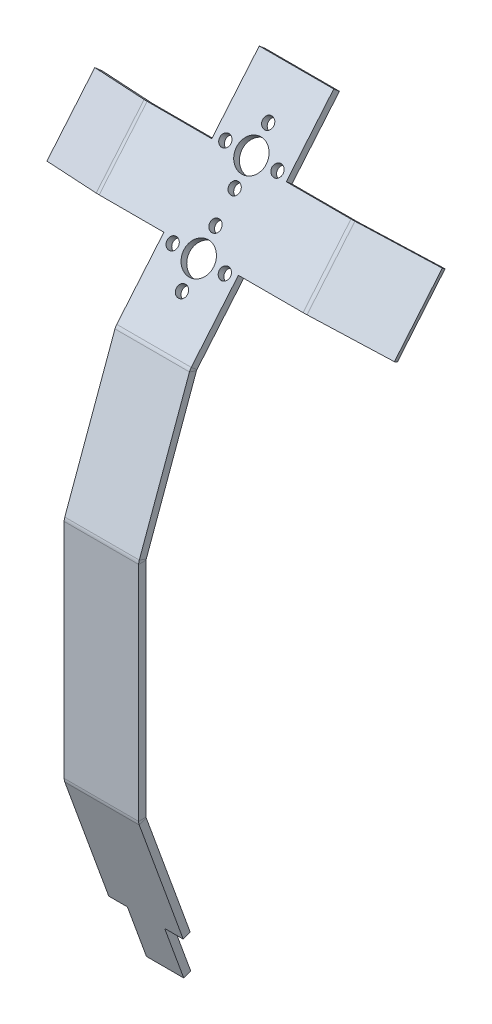
SolidWorks part; units mm, degrees
note: The reader was unsure of these and kept them because the rebuilt part matched: flange length of "Edge-Flange1", "Edge-Flange2", "Edge-Flange3", "Edge-Flange4".
ref_plane "Front Plane" through (0, 0, 0) normal (0, 0, 1) x (1, 0, 0)
ref_plane "Top Plane" through (0, 0, 0) normal (0, 1, 0) x (1, 0, 0)
ref_plane "Right Plane" through (0, 0, 0) normal (1, 0, 0) x (0, 0, -1)
sketch "Sketch1" plane through (0, 0, 0) normal (0, 0, 1) x (1, 0, 0)
  line L1 (-10, -30) -> (10, -30)
  line L2 (-10, -30) -> (-10, 30)
  line L3 (-10, 30) -> (10, 30)
  line L4 (10, -30) -> (10, 30)
  line L5 (-10, -30) -> (10, 30) construction
  line L6 (-10, 30) -> (10, -30) construction
  point P0 (0, 0)
  dimension "D1" = 20
  dimension "D2" = 60
base flange "Base-Flange1" sketch "Sketch1" thickness 2 reverse thickness direction no parameters "D1"=0.7366
sketch "Sketch2" plane through (0, 0, 0) normal (0, 0, 1) x (1, 0, 0)
  line L0 (0, 30) -> (0, -30) construction
  line L1 (10, 30) -> (-10, 30) construction
  line L2 (-10, -30) -> (10, -30) construction
  line L3 (-10, 0) -> (10, 0) construction
  line L4 (-10, 30) -> (-10, -30) construction
  line L5 (10, -30) -> (10, 30) construction
  circle A0 centre (0, 11) radius 4
  circle A2 centre (0, 18) radius 1.5
  circle A3 centre (7, 11) radius 1.5
  circle A4 centre (0, 4) radius 1.5
  circle A5 centre (-7, 11) radius 1.5
  circle A6 centre (0, -18) radius 1.5
  circle A7 centre (7, -11) radius 1.5
  circle A8 centre (0, -4) radius 1.5
  circle A9 centre (0, -11) radius 4
  circle A10 centre (-7, -11) radius 1.5
  point P20 (0, 11)
  dimension "D1" = 8
  dimension "D3" = 7
  dimension "D4" = 3
  dimension "D2" = 11
  dimension "D5" = 4
extrude "Cut-Extrude1" [suppressed] cut sketch "Sketch2" against normal blind 2 contours A0 | A2 | A3 | A4 | A5 | A9 | A8 | A7 | A10 | A6
edge flange "Edge-Flange1" sketch "Sketch9" flange angle 160 flange length 40 flange position material outside bend radius 0.7366 thickness 2 relief rectangular parameters "D6"=10
sketch "Sketch9" plane through (0, 30, -2) normal (0, 0.342, 0.9397) x (1, 0, 0)
  line L0 (10, 0) -> (-10, 0) construction
  line L1 (10, 0) -> (-10, 0)
  line L2 (-10, 0) -> (-10, 39.6473)
  line L3 (-10, 39.6473) -> (10, 39.6473)
  line L4 (10, 39.6473) -> (10, 0)
bend "EdgeBend1" bend radius 0.7366 bend angle 20 parameters "D5"=1
edge flange "Edge-Flange2" sketch "Sketch12" flange angle 160 flange length 50 flange position material outside bend radius 0.7366 thickness 2 relief rectangular parameters "D6"=10
sketch "Sketch12" plane through (0, -30, -2) normal (0, -0.342, 0.9397) x (-1, 0, 0)
  line L0 (10, 0) -> (-10, 0) construction
  line L1 (10, 0) -> (-10, 0)
  line L2 (-10, 0) -> (-10, 49.6473)
  line L3 (-10, 49.6473) -> (10, 49.6473)
  line L4 (10, 49.6473) -> (10, 0)
bend "EdgeBend2" bend radius 0.7366 bend angle 20 parameters "D5"=2
edge flange "Edge-Flange3" sketch "Sketch15" flange angle 160 flange length 60 flange position material outside bend radius 0.7366 thickness 2 relief rectangular parameters "D6"=10
sketch "Sketch15" plane through (0, 67.2563, -15.5602) normal (0, 0.6428, 0.766) x (1, 0, 0)
  line L0 (10, 0) -> (-10, 0) construction
  line L1 (10, 0) -> (-10, 0)
  line L2 (-10, 0) -> (-10, 19.8237)
  line L3 (-10, 59.6473) -> (10, 59.6473)
  line L4 (10, 59.6473) -> (10, 39.8237)
  line L5 (7.586, 29.8237) -> (-46.5431, 29.8237) construction
  line L6 (10, 19.8237) -> (10, 0)
  line L7 (27.5, 19.8237) -> (10, 19.8237)
  line L8 (27.5, 19.8237) -> (27.5, 39.8237)
  line L9 (27.5, 39.8237) -> (10, 39.8237)
  line L11 (27.5, 19.8237) -> (10, 39.8237) construction
  line L12 (27.5, 39.8237) -> (10, 19.8237) construction
  line L13 (-27.5, 19.8237) -> (-10, 19.8237)
  line L14 (-27.5, 19.8237) -> (-27.5, 39.8237)
  line L15 (-27.5, 39.8237) -> (-10, 39.8237)
  line L17 (-27.5, 19.8237) -> (-10, 39.8237) construction
  line L18 (-27.5, 39.8237) -> (-10, 19.8237) construction
  line L19 (-10, 39.8237) -> (-10, 59.6473)
  point P6 (18.75, 29.8237)
  point P12 (-18.75, 29.8237)
  dimension "D1" = 20
  dimension "D2" = 17.5
bend "EdgeBend3" bend radius 0.7366 bend angle 20 parameters "D5"=3
sketch "Sketch16" plane through (0, -3.5506, 9.7552) normal (0, -0.342, 0.9397) x (1, 0, 0)
  line L1 (-10, -78.5222) -> (-5, -78.5222)
  line L2 (-10, -78.5222) -> (-10, -63.5222)
  line L3 (-10, -63.5222) -> (-5, -63.5222)
  line L4 (-5, -78.5222) -> (-5, -63.5222)
  line L5 (10, -78.5222) -> (5, -78.5222)
  line L6 (10, -78.5222) -> (10, -63.5222)
  line L7 (10, -63.5222) -> (5, -63.5222)
  line L8 (5, -78.5222) -> (5, -63.5222)
  dimension "D1" = 10
  dimension "D2" = 15
edge flange "Edge-Flange4" sketch "Sketch21" flange profiles "Sketch21", "Sketch22" flange angle 160 flange length 20 flange position material outside bend radius 0.7366 thickness 2 relief rectangular parameters "D6"=10, "D8"=1
sketch "Sketch21" plane through (27.5, 20.1268, 23.9862) normal (0.342, 0.604, 0.7198) x (0, -0.766, 0.6428)
  line L0 (-81.3469, 0) -> (-101.3469, 0) construction
  line L1 (-81.3469, 0) -> (-101.3469, 0)
  line L2 (-101.3469, 0) -> (-101.3469, 19.6473)
  line L3 (-101.3469, 19.6473) -> (-81.3469, 19.6473)
  line L4 (-81.3469, 19.6473) -> (-81.3469, 0)
sketch "Sketch22" plane through (-27.5, 20.1268, 23.9862) normal (-0.342, 0.604, 0.7198) x (0, 0.766, -0.6428)
  line L0 (101.3469, 0) -> (81.3469, 0) construction
  line L1 (101.3469, 0) -> (81.3469, 0)
  line L2 (81.3469, 0) -> (81.3469, 19.6473)
  line L3 (81.3469, 19.6473) -> (101.3469, 19.6473)
  line L4 (101.3469, 19.6473) -> (101.3469, 0)
bend "EdgeBend4" bend radius 0.7366 bend angle 20 parameters "D5"=4
bend "EdgeBend5" bend radius 0.7366 bend angle 20 parameters "D5"=5
extrude "Cut-Extrude2" cut sketch "Sketch16" against normal through all normal cut yes
sketch "Sketch23" plane through (0, 20.1268, 23.9862) normal (0, -0.6428, -0.766) x (-1, 0, 0)
  line L0 (0, 61.5232) -> (0, 121.1706) construction
  line L1 (-10, 61.5232) -> (10, 61.5232) construction
  line L2 (-10, 121.1706) -> (10, 121.1706) construction
  line L3 (-24.4149, 91.3469) -> (26.8084, 91.3469) construction
  circle A0 centre (0, 102.3469) radius 4
  circle A1 centre (0, 109.3469) radius 1.5
  circle A2 centre (7, 102.3469) radius 1.5
  circle A3 centre (0, 95.3469) radius 1.5
  circle A4 centre (-7, 102.3469) radius 1.5
  circle A5 centre (-7, 80.3469) radius 1.5
  circle A6 centre (7, 80.3469) radius 1.5
  circle A7 centre (0, 80.3469) radius 4
  circle A8 centre (0, 87.3469) radius 1.5
  circle A9 centre (0, 73.3469) radius 1.5
  point P12 (0, 91.3469)
  point P22 (0, 102.3469)
  dimension "D1" = 8
  dimension "D2" = 3
  dimension "D3" = 7
  dimension "D4" = 11
  dimension "D5" = 4
extrude "Cut-Extrude3" cut sketch "Sketch23" against normal blind 2 normal cut yes
sketch "Bend-Lines1" [suppressed] plane through (0, 0, 0) normal (0, 1, 0) x (1, 0, 0)
sketch "Bounding-Box1" [suppressed] plane through (0, 0, 0) normal (0, 1, 0) x (1, 0, 0)
sheet metal parameters "Sheet-Metal2" thickness 2 parameters "D1"=0.7366
flat pattern "Flat-Pattern2" [suppressed]
sketch "Bend-Lines2" plane through (0, 0, 0) normal (0, 1, 0) x (1, 0, 0)
sketch3d "Bounding-Box2" [suppressed]
  line L0 (10, 30, 0) -> (10, -30, 0) construction
  line L1 (-10, 30, 0) -> (-10, -30, 0) construction
  line L2 (10, 30, 0) -> (-10, 30, 0) construction
  line L3 (10, -30, 0) -> (-10, -30, 0) construction
sheet metal parameters "Sheet-Metal3" thickness 2 parameters "D1"=0.7366
flat pattern "Flat-Pattern2"
sketch "Bend-Lines2" plane through (0, 0, 0) normal (0, 1, 0) x (1, 0, 0)
sketch3d "Bounding-Box2" [suppressed]
  line L0 (10, 30, 0) -> (10, -30, 0) construction
  line L1 (-10, 30, 0) -> (-10, -30, 0) construction
  line L2 (10, 30, 0) -> (-10, 30, 0) construction
  line L3 (10, -30, 0) -> (-10, -30, 0) construction
sheet metal parameters "Sheet-Metal4" thickness 2 parameters "D1"=0.7366
flat pattern "Flat-Pattern2" [suppressed]
sketch "Bend-Lines2" plane through (0, 0, 0) normal (0, 0, 1) x (1, 0, 0)
  line L0 (10, 30.2156) -> (-10, 30.2156) construction
  line L1 (10, 30.2156) -> (-10, 30.2156) construction
sketch3d "Bounding-Box2" [suppressed]
  line L0 (10, 74.9877, 0) -> (10, -30, 0) construction
  line L1 (-10, 74.9877, 0) -> (-10, -30, 0) construction
  line L2 (10, 74.9877, 0) -> (-10, 74.9877, 0) construction
  line L3 (10, -30, 0) -> (-10, -30, 0) construction
bend of the flat pattern "Flatten-<EdgeBend1>1"
sheet metal parameters "Sheet-Metal5" thickness 2 parameters "D1"=0.7366
flat pattern "Flat-Pattern2" [suppressed]
sketch "Bend-Lines2" plane through (0, 0, 0) normal (0, 0, 1) x (1, 0, 0)
  line L0 (10, 30.2323) -> (-10, 30.2323) construction
  line L1 (10, 30.2323) -> (-10, 30.2323) construction
  line L2 (-10, -30.1732) -> (10, -30.1732) construction
  line L3 (-10, -30.1732) -> (10, -30.1732) construction
sketch3d "Bounding-Box2" [suppressed]
  line L0 (10, 69.9845, 0) -> (10, -84.9938, 0) construction
  line L1 (-10, 69.9845, 0) -> (-10, -84.9938, 0) construction
  line L2 (10, 69.9845, 0) -> (-10, 69.9845, 0) construction
  line L3 (10, -84.9938, 0) -> (-10, -84.9938, 0) construction
bend of the flat pattern "Flatten-<EdgeBend2>1"
bend of the flat pattern "Flatten-<EdgeBend1>1"
sheet metal parameters "Sheet-Metal6" thickness 2 parameters "D1"=0.7366
flat pattern "Flat-Pattern2" [suppressed]
sketch "Bend-Lines2" plane through (0, 0, 0) normal (0, 0, 1) x (1, 0, 0)
  line L0 (10, 30.1732) -> (-10, 30.1732) construction
  line L1 (10, 30.1732) -> (-10, 30.1732) construction
  line L2 (-10, -30.1732) -> (10, -30.1732) construction
  line L3 (-10, -30.1732) -> (10, -30.1732) construction
  line L4 (10, 70.167) -> (-10, 70.167) construction
  line L5 (10, 70.167) -> (-10, 70.167) construction
sketch3d "Bounding-Box2" [suppressed]
  line L0 (20, 119.9742, 0) -> (20, -79.9938, 0) construction
  line L1 (-20, 119.9742, 0) -> (-20, -79.9938, 0) construction
  line L2 (20, 119.9742, 0) -> (-20, 119.9742, 0) construction
  line L3 (20, -79.9938, 0) -> (-20, -79.9938, 0) construction
bend of the flat pattern "Flatten-<EdgeBend2>1"
bend of the flat pattern "Flatten-<EdgeBend3>1"
bend of the flat pattern "Flatten-<EdgeBend1>1"
sheet metal parameters "Sheet-Metal7" thickness 2 parameters "D1"=0.7366
flat pattern "Flat-Pattern2" [suppressed]
sketch "Bend-Lines2" plane through (0, 0, 0) normal (0, 0, 1) x (1, 0, 0)
  line L0 (12.5, 30.1732) -> (-12.5, 30.1732) construction
  line L1 (12.5, 30.1732) -> (-12.5, 30.1732) construction
  line L2 (-12.5, -30.1732) -> (12.5, -30.1732) construction
  line L3 (-12.5, -30.1732) -> (12.5, -30.1732) construction
  line L4 (12.5, 70.167) -> (-12.5, 70.167) construction
  line L5 (12.5, 70.167) -> (-12.5, 70.167) construction
  line L6 (-30.1732, 110.1639) -> (-30.1732, 90.1639) construction
  line L7 (30.1732, 90.1639) -> (30.1732, 110.1639) construction
  line L8 (-30.1732, 110.1639) -> (-30.1732, 90.1639) construction
  line L9 (30.1732, 90.1639) -> (30.1732, 110.1639) construction
sketch3d "Bounding-Box2" [suppressed]
  line L0 (49.9938, 129.9875, 0) -> (49.9938, -79.9938, 0) construction
  line L1 (-49.9938, 129.9875, 0) -> (-49.9938, -79.9938, 0) construction
  line L2 (49.9938, 129.9875, 0) -> (-49.9938, 129.9875, 0) construction
  line L3 (49.9938, -79.9938, 0) -> (-49.9938, -79.9938, 0) construction
bend of the flat pattern "Flatten-<EdgeBend2>1"
bend of the flat pattern "Flatten-<EdgeBend3>1"
bend of the flat pattern "Flatten-<EdgeBend5>2"
bend of the flat pattern "Flatten-<EdgeBend4>2"
bend of the flat pattern "Flatten-<EdgeBend1>1"
sheet metal parameters "Sheet-Metal8" thickness 2 parameters "D1"=0.7366
flat pattern "Flat-Pattern2" [suppressed]
sketch "Bend-Lines2" plane through (0, 0, 0) normal (0, 0, 1) x (1, 0, 0)
  line L0 (10, 30.1732) -> (-10, 30.1732) construction
  line L1 (10, 30.1732) -> (-10, 30.1732) construction
  line L2 (-10, -30.1732) -> (10, -30.1732) construction
  line L3 (-10, -30.1732) -> (10, -30.1732) construction
  line L4 (10, 70.167) -> (-10, 70.167) construction
  line L5 (10, 70.167) -> (-10, 70.167) construction
  line L6 (-20.0871, 105.1572) -> (-20.0871, 85.1572) construction
  line L7 (20.0871, 85.1572) -> (20.0871, 105.1572) construction
  line L8 (-20.0871, 105.1572) -> (-20.0871, 85.1572) construction
  line L9 (20.0871, 85.1572) -> (20.0871, 105.1572) construction
sketch3d "Bounding-Box2" [suppressed]
  line L0 (39.9992, 119.9742, 0) -> (39.9992, -79.9938, 0) construction
  line L1 (-39.9992, 119.9742, 0) -> (-39.9992, -79.9938, 0) construction
  line L2 (39.9992, 119.9742, 0) -> (-39.9992, 119.9742, 0) construction
  line L3 (39.9992, -79.9938, 0) -> (-39.9992, -79.9938, 0) construction
bend of the flat pattern "Flatten-<EdgeBend2>1"
bend of the flat pattern "Flatten-<EdgeBend3>1"
bend of the flat pattern "Flatten-<EdgeBend4>1"
bend of the flat pattern "Flatten-<EdgeBend5>1"
bend of the flat pattern "Flatten-<EdgeBend1>1"
sheet metal parameters "Sheet-Metal9" thickness 2 parameters "D1"=0.7366
flat pattern "Flat-Pattern2"
sketch "Bend-Lines2" plane through (0, 0, 0) normal (0, 0, 1) x (1, 0, 0)
  line L0 (10, 30.1732) -> (-10, 30.1732) construction
  line L1 (10, 30.1732) -> (-10, 30.1732) construction
  line L2 (-10, -30.1732) -> (10, -30.1732) construction
  line L3 (-10, -30.1732) -> (10, -30.1732) construction
  line L4 (10, 70.167) -> (-10, 70.167) construction
  line L5 (10, 70.167) -> (-10, 70.167) construction
  line L6 (-27.6732, 110.1639) -> (-27.6732, 90.1639) construction
  line L7 (27.6732, 90.1639) -> (27.6732, 110.1639) construction
  line L8 (-27.6732, 110.1639) -> (-27.6732, 90.1639) construction
  line L9 (27.6732, 90.1639) -> (27.6732, 110.1639) construction
sketch3d "Bounding-Box2" [suppressed]
  line L0 (47.4938, 129.9875, 0) -> (47.4938, -79.9938, 0) construction
  line L1 (-47.4938, 129.9875, 0) -> (-47.4938, -79.9938, 0) construction
  line L2 (47.4938, 129.9875, 0) -> (-47.4938, 129.9875, 0) construction
  line L3 (47.4938, -79.9938, 0) -> (-47.4938, -79.9938, 0) construction
bend of the flat pattern "Flatten-<EdgeBend2>1"
bend of the flat pattern "Flatten-<EdgeBend3>1"
bend of the flat pattern "Flatten-<EdgeBend5>2"
bend of the flat pattern "Flatten-<EdgeBend4>2"
bend of the flat pattern "Flatten-<EdgeBend1>1"
